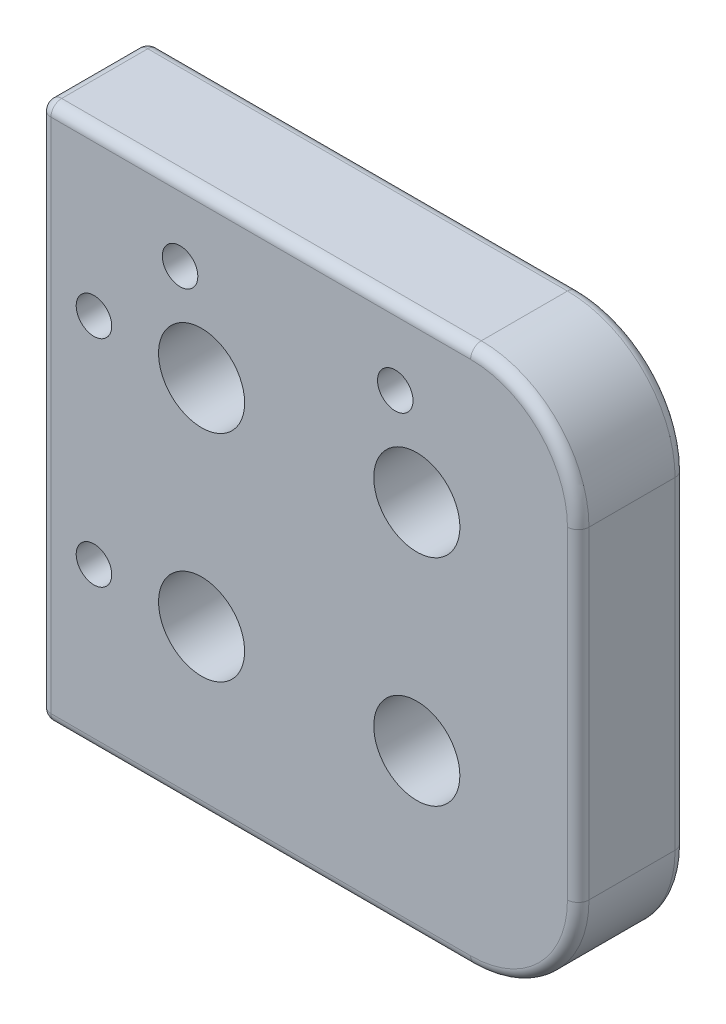
SolidWorks part; units mm, degrees
ref_plane "前视基准面" through (0, 0, 0) normal (0, 0, 1) x (1, 0, 0)
ref_plane "上视基准面" through (0, 0, 0) normal (0, 1, 0) x (1, 0, 0)
ref_plane "右视基准面" through (0, 0, 0) normal (1, 0, 0) x (0, 0, -1)
sketch "草图1" plane through (0, 0, 0) normal (0, 0, 1) x (1, 0, 0)
  line L1 (-25, -25) -> (25, -25) construction
  line L2 (-25, -25) -> (-25, 25)
  line L3 (-25, 25) -> (25, 25) construction
  line L4 (25, -25) -> (25, 25) construction
  line L5 (-25, -25) -> (25, 25) construction
  line L6 (-25, 25) -> (25, -25) construction
  line L7 (-25, 25) -> (25, 25)
  line L8 (-25, -25) -> (25, -25)
  line L9 (25, -25) -> (25, 25)
  point P0 (0, 0)
  dimension "D1" = 50
  dimension "D2" = 50
extrude "凸台-拉伸1" add sketch "草图1" along normal blind 10
sketch "草图2" plane through (0, 0, 10) normal (0, 0, 1) x (1, 0, 0)
  line L0 (0, 0) -> (50000, 0) construction
  line L7 (-10, -10) -> (-10, 10) construction
  line L8 (-10, 10) -> (15, 10) construction
  line L9 (15, -10) -> (15, 10) construction
  line L10 (-10, -10) -> (15, 10) construction
  line L11 (-10, 10) -> (15, -10) construction
  line L12 (2.5, 0) -> (2.5, 50000) construction
  line L13 (-10, -10) -> (15, -10) construction
  circle A4 centre (-10, 10) radius 1.6
  circle A5 centre (15, 10) radius 1.6
  circle A6 centre (15, -10) radius 1.6
  circle A7 centre (-10, -10) radius 1.6
  point P0 (2.5, 0)
  dimension "D3" = 2.5
  dimension "D4" = 3.2
  dimension "D1" = 20
  dimension "D2" = 25
extrude "切除-拉伸1" [suppressed] cut sketch "草图2" against normal through all
fillet "圆角1" radius 10 2 edges at (25, -25, 5) (25, 25, 5)
fillet "圆角2" radius 1 14 edges at (-5, -25, 0) (-5, -25, 10) (-25, 0, 0) (-5, 25, 0) (-5, 25, 10) (-25, 0, 10) (-25, -25, 5) (-25, 25, 5) (22.0711, -22.0711, 0) (25, 0, 0) (22.0711, 22.0711, 0) (22.0711, -22.0711, 10) (25, 0, 10) (22.0711, 22.0711, 10)
sketch "草图3" plane through (0, 0, 10) normal (0, 0, 1) x (1, 0, 0)
  line L0 (0, 30.5262) -> (0, -32.5462) construction
  line L1 (-34.1369, 0) -> (41.2066, 0) construction
  circle A0 centre (-10, 10) radius 4
  circle A1 centre (10, 10) radius 4
  circle A2 centre (10, -10) radius 4
  circle A3 centre (-10, -10) radius 4
  dimension "D1" = 8
  dimension "D2" = 10
  dimension "D3" = 10
extrude "切除-拉伸2" cut sketch "草图3" against normal blind 10
sketch "草图4" plane through (0, 0, 10) normal (0, 0, 1) x (1, 0, 0)
  line L1 (-10, 10) -> (10, 10) construction
  line L2 (-10, -10) -> (10, -10) construction
  circle A0 centre (-20, -10) radius 1.65
  circle A1 centre (-10, -10) radius 4 construction
  circle A2 centre (-20, 10) radius 1.65
  circle A4 centre (-10, 10) radius 4 construction
  circle A5 centre (-12, 18) radius 1.65
  circle A6 centre (8, 18) radius 1.65
  dimension "D1" = 3.3
  dimension "D2" = 10
  dimension "D3" = 3.3
  dimension "D4" = 10
  dimension "D5" = 3.3
  dimension "D6" = 3.3
  dimension "D7" = 20
  dimension "D8" = 2
  dimension "D9" = 8
extrude "切除-拉伸3" cut sketch "草图4" against normal blind 10
equation "\"3。2\"=3.16193"
